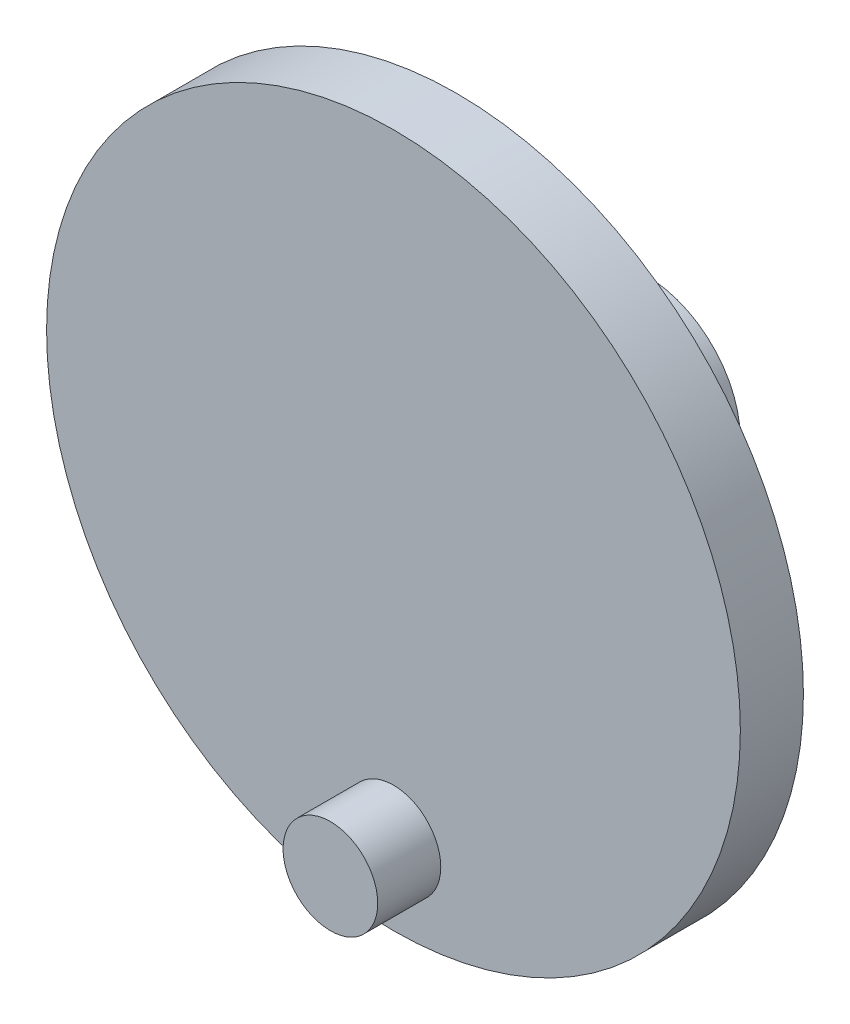
SolidWorks part; units mm, degrees
ref_plane "Front Plane" through (0, 0, 0) normal (0, 0, 1) x (1, 0, 0)
ref_plane "Top Plane" through (0, 0, 0) normal (0, 1, 0) x (1, 0, 0)
ref_plane "Right Plane" through (0, 0, 0) normal (1, 0, 0) x (0, 0, -1)
sketch "Sketch_Cam" plane through (0, 0, 0) normal (0, 0, 1) x (1, 0, 0)
  line L0 (0, -42.5) -> (0, 0) construction
  circle A0 centre (0, 0) radius 55
  circle A1 centre (0, -42.5) radius 7.5
  dimension "D2" = 15
  dimension "D1" = 42.5
  dimension "D3" = 5
extrude "Cam" add sketch "Sketch_Cam" against normal blind 10 contours A1 | A0 A1 region at (0, 0.8053, 0) region at (0, -42.5, 0)
extrude "Cam Pivot" add sketch "Sketch_Cam<3>" along normal blind 10 contours A1 region at (0, -42.5, 0)
sketch "Sketch_Cam<3>" plane through (0, 0, 0) normal (0, 0, 1) x (1, 0, 0) same geometry as "Sketch_Cam"
sketch "Sketch_Spin Shaft" plane through (0, 0, 0) normal (0, 0, 1) x (1, 0, 0)
  circle A0 centre (0, 0) radius 15
  dimension "D1" = 30
extrude "Spin Shaft" add sketch "Sketch_Spin Shaft" against normal offset from surface (40 mm away) 30 up to face at (55, 0, -10) offset beyond the face yes
equation "\"D1@Sketch_Cam\"=85/2"
